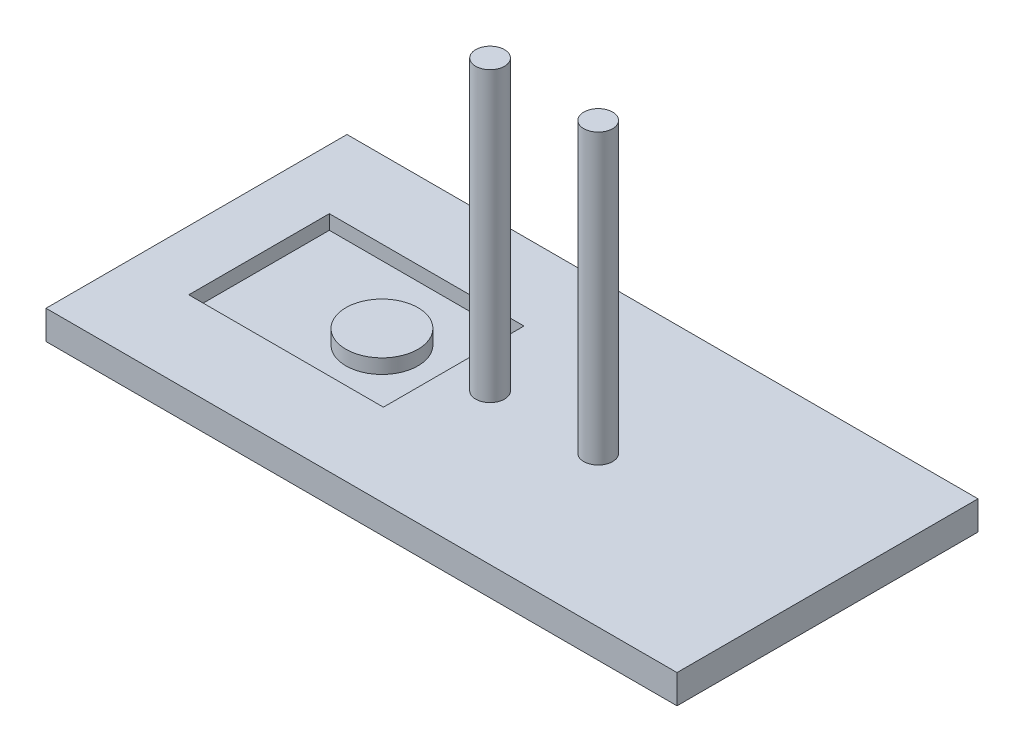
SolidWorks part; units mm, degrees
ref_plane "Front Plane" through (0, 0, 0) normal (0, 0, 1) x (1, 0, 0)
ref_plane "Top Plane" through (0, 0, 0) normal (0, 1, 0) x (1, 0, 0)
ref_plane "Right Plane" through (0, 0, 0) normal (1, 0, 0) x (0, 0, -1)
sketch "Sketch1" plane through (0, 0, 0) normal (0, 1, 0) x (1, 0, 0)
  line L0 (-43.7678, 0) -> (43.7678, 0) construction
  line L1 (-43.7678, -20.877) -> (43.7678, -20.877)
  line L2 (-43.7678, -20.877) -> (-43.7678, 20.877)
  line L3 (-43.7678, 20.877) -> (43.7678, 20.877)
  line L4 (43.7678, -20.877) -> (43.7678, 20.877)
  line L5 (-43.7678, -20.877) -> (43.7678, 20.877) construction
  line L6 (-43.7678, 20.877) -> (43.7678, -20.877) construction
  line L8 (-35.4791, -9.3605) -> (-8.4791, -9.3605)
  line L9 (-35.4791, -9.3605) -> (-35.4791, 10.1395)
  line L10 (-35.4791, 10.1395) -> (-8.4791, 10.1395)
  line L11 (-8.4791, -9.3605) -> (-8.4791, 10.1395)
  circle A0 centre (-18.039, 0) radius 5
  circle A1 centre (-3.039, 0) radius 10
  circle A2 centre (-3.039, 0) radius 5
  circle A3 centre (11.961, 0) radius 10
  circle A4 centre (11.961, 0) radius 5
  circle A5 centre (11.961, 0) radius 2
  circle A7 centre (-3.039, 0) radius 2
  point P0 (0, 0)
  point P20 (0, 0)
  point P26 (0, 0)
  point P27 (0, 0)
  point P28 (0, 0)
  point P29 (0, 0)
  point P30 (0, 0)
  point P31 (0, 0)
  point P32 (0, 0)
  point P33 (0, 0)
  point P34 (0, 0)
  dimension "D1" = 10
  dimension "D2" = 20
  dimension "D5" = 4
  dimension "D3" = 19.5
  dimension "D4" = 27
sketch "Sketch2" plane through (0, 0, 0) normal (0, 1, 0) x (1, 0, 0)
  line L2 (-43.7678, -20.877) -> (43.7678, -20.877)
  line L3 (-43.7678, -20.877) -> (-43.7678, 20.877)
  line L4 (-43.7678, 20.877) -> (43.7678, 20.877)
  line L5 (43.7678, -20.877) -> (43.7678, 20.877)
  line L6 (-43.7678, -20.877) -> (43.7678, 20.877) construction
  line L7 (-43.7678, 20.877) -> (43.7678, -20.877) construction
  point P1 (0, 0)
  point P2 (0, 0)
  point P14 (0, 0)
extrude "Boss-Extrude1" add sketch "Sketch2" against normal blind 4 contours L2 L5 L4 L3 region at (0, 0, 0)
extrude "Boss-Extrude2" add sketch "Sketch1" along normal blind 40 contours A5 | A7 region at (11.961, 0, 0)
extrude "Cut-Extrude1" cut sketch "Sketch1<3>" against normal blind 2 contours A1 L11 L10 L9 L8 A0 | L11 A1 region at (-24.3562, 0, -0.5205) region at (-10.3441, 0, 0)
sketch "Sketch1<3>" plane through (0, 0, 0) normal (0, 1, 0) x (1, 0, 0) same geometry as "Sketch1"
equation "\"smalldia\"=10"
equation "\"D1@Sketch1\"=\"smalldia\""
equation "\"largedia\"=20"
equation "\"D2@Sketch1\"=\"largedia\""
